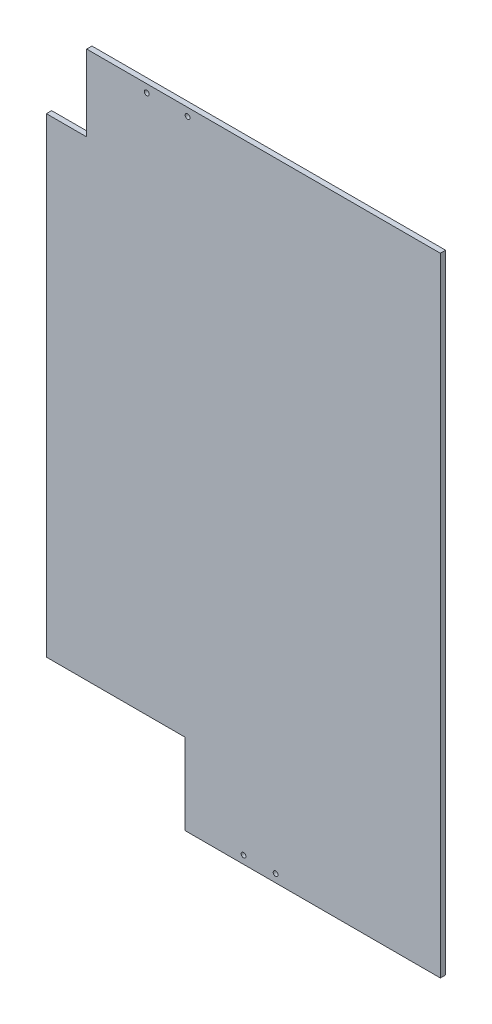
SolidWorks part; units mm, degrees
material "Balsa"
ref_plane "Front Plane" through (0, 0, 0) normal (0, 0, 1) x (1, 0, 0)
ref_plane "Top Plane" through (0, 0, 0) normal (0, 1, 0) x (1, 0, 0)
ref_plane "Right Plane" through (0, 0, 0) normal (1, 0, 0) x (0, 0, -1)
sketch "Sketch1" plane through (0, 0, 0) normal (0, 0, 1) x (1, 0, 0)
  line L0 (-5.7823, -13) -> (25.5, -13)
  line L2 (-5.7823, 1) -> (-5.7823, -13)
  line L5 (24.5, -14) -> (-24.5, -14) construction
  line L6 (272.4388, -265) -> (272.4388, 30)
  line L7 (-5.8246, -265) -> (65.6329, -265)
  line L8 (-5.8246, -265) -> (-5.8246, -225)
  line L11 (-5.8246, -265) -> (65.6329, -225) construction
  line L12 (-5.8246, -225) -> (65.6329, -265) construction
  line L15 (272.4388, -265) -> (25.5, -265)
  line L16 (25.5, 1) -> (25.5, -265)
  line L17 (-5.8246, -225) -> (25.5, -225)
  line L18 (-24.5, -224) -> (24.5, -224) construction
  line L19 (-5.7823, 1) -> (25.5, 1)
  line L20 (24.5, -224) -> (24.5, -14) construction
  line L21 (-85.1981, 31) -> (50.7481, 31) construction
  line L23 (25.5, 1) -> (25.5, 30)
  line L24 (25.5, 30) -> (272.4388, 30)
  line L28 (26.2777, -266) -> (-26.2882, -266) construction
  line L30 (-63.4467, 81) -> (255.5737, 81) construction
  line L31 (50.7481, 30) -> (272.4388, 30)
  line L32 (50.7481, 30) -> (50.7481, 77.7)
  line L33 (50.7481, 77.7) -> (272.4388, 77.7)
  line L34 (272.4388, 30) -> (272.4388, 77.7)
  line L35 (50.7481, 30) -> (272.4388, 77.7) construction
  line L36 (50.7481, 77.7) -> (272.4388, 30) construction
  line L37 (255.5737, -319) -> (-63.4467, -319) construction
  line L38 (272.4388, -265) -> (112.4388, -265)
  line L39 (272.4388, -265) -> (272.4388, -315.7)
  line L40 (272.4388, -315.7) -> (112.4388, -315.7)
  line L41 (112.4388, -265) -> (112.4388, -315.7)
  line L42 (272.4388, -265) -> (112.4388, -315.7) construction
  line L43 (272.4388, -315.7) -> (112.4388, -265) construction
  line L44 (50.7481, 31) -> (50.7481, -269) construction
  point P4 (32.4695, -6)
  point P10 (29.9042, -245)
  point P15 (48.1318, -132)
  point P24 (48.1318, 15.5)
  point P36 (161.5934, 53.85)
  point P42 (192.4388, -290.35)
  dimension "D1" = 1
  dimension "D2" = 1
  dimension "D3" = 1
  dimension "D4" = 1
  dimension "D5" = 1
  dimension "D6" = 31.3246
  dimension "D8" = 3.3
  dimension "D9" = 160
  dimension "D10" = 3.3
extrude "Boss-Extrude1" add sketch "Sketch1" along normal blind 3.3 contours L24 L23 L16 L7 L15 L6 | L19 L2 L0 L16 | L17 L8 L7 L16 | L24 L34 L33 L32 | L15 L41 L40 L39 region at (9.8589, -6, 0) region at (148.9694, -117.5, 0) region at (9.8377, -245, 0) region at (161.5934, 53.85, 0) region at (192.4388, -290.35, 0)
sketch "Sketch2" plane through (0, 0, 0) normal (0, 0, -1) x (-1, 0, 0)
  circle A0 centre (-113.9984, 72.7) radius 1.5
  circle A1 centre (-88.397, 72.7) radius 1.5
  circle A2 centre (-169.1689, -310.7) radius 1.5
  circle A3 centre (-149.0844, -310.7) radius 1.5
  dimension "D1" = 3
  dimension "D2" = 3
  dimension "D3" = 3
  dimension "D4" = 3
extrude "Cut-Extrude1" cut sketch "Sketch2" against normal through all
sketch "Sketch3" plane through (119.3915, 0, 256.0358) normal (0.4226, 0, 0.9063) x (0.9063, 0, -0.4226)
  line L1 (293.4595, -146) -> (268.9595, -146)
  line L2 (293.4595, -146) -> (293.4595, -92)
  line L3 (293.4595, -92) -> (268.9595, -92)
  line L4 (268.9595, -146) -> (268.9595, -92)
  line L5 (293.4595, -146) -> (268.9595, -92) construction
  line L6 (293.4595, -92) -> (268.9595, -146) construction
  point P4 (281.2095, -119)
sketch "Sketch4" plane through (0, 0, 0) normal (0, 0, -1) x (-1, 0, 0)
  line L1 (-272.4388, -92) -> (-242.4388, -92)
  line L2 (-272.4388, -92) -> (-272.4388, -146)
  line L3 (-272.4388, -146) -> (-242.4388, -146)
  line L4 (-242.4388, -92) -> (-242.4388, -146)
  line L5 (-272.4388, -92) -> (-242.4388, -146) construction
  line L6 (-272.4388, -146) -> (-242.4388, -92) construction
  line L7 (-272.4388, -315.7) -> (-272.4388, 77.7) construction
  point P4 (-257.4388, -119)
  dimension "D1" = 54
  dimension "D2" = 30
sketch "Sketch5" plane through (0, 0, 0) normal (0, 0, -1) x (-1, 0, 0)
  line L0 (5.7823, 1) -> (-25.5, 1) construction
  line L1 (5.8246, -265) -> (-25.5, -265)
  line L2 (5.8246, -265) -> (5.8246, 1)
  line L3 (5.8246, 1) -> (-25.5, 1)
  line L4 (-25.5, -265) -> (-25.5, 1)
  line L5 (5.8246, -265) -> (-25.5, 1) construction
  line L6 (5.8246, 1) -> (-25.5, -265) construction
  line L7 (-25.5, 1) -> (-25.5, 30) construction
  point P4 (-9.8377, -132)
extrude "Cut-Extrude4" cut sketch "Sketch5" against normal blind 10
